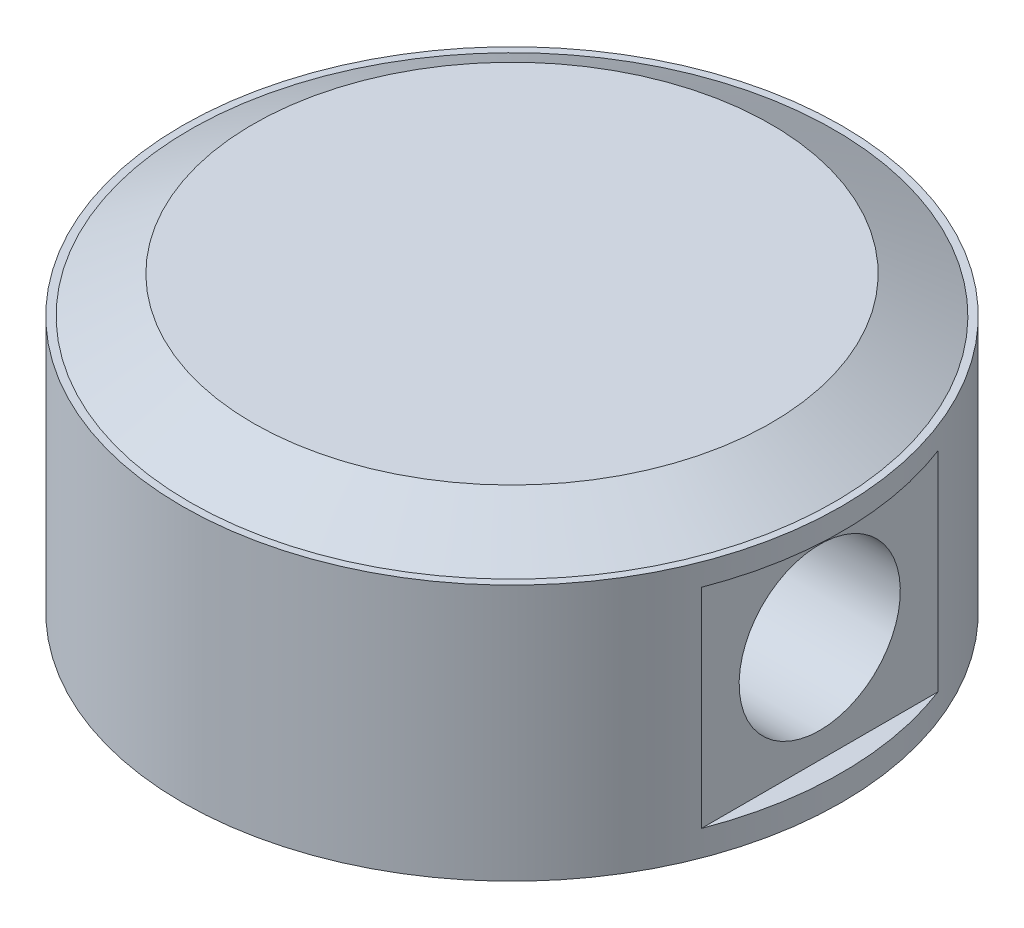
SolidWorks part; units mm, degrees
ref_plane "Front Plane" through (0, 0, 0) normal (0, 0, 1) x (1, 0, 0)
ref_plane "Top Plane" through (0, 0, 0) normal (0, 1, 0) x (1, 0, 0)
ref_plane "Right Plane" through (0, 0, 0) normal (1, 0, 0) x (0, 0, -1)
sketch "Sketch3" plane through (0, 0, 0) normal (0, 0, 1) x (1, 0, 0)
  line L0 (0, 0) -> (0, -5)
  line L1 (0, -5) -> (23.005, -5)
  line L2 (23.005, -5) -> (37, -13.08)
  line L3 (37, -13.08) -> (37, -23.08)
  line L4 (37, -23.08) -> (42, -23.08)
  line L5 (42, -23.08) -> (42, -40)
  line L6 (42, -40) -> (45, -40)
  line L8 (44, -5) -> (35.3397, 0)
  line L9 (35.3397, 0) -> (0, 0)
  line L10 (44, -5) -> (45, -5)
  line L12 (45, -5) -> (45, -40)
  dimension "D1" = 5
  dimension "D2" = 5
  dimension "D3" = 3
  dimension "D4" = 45
  dimension "D5" = 10
  dimension "D6" = 35
  dimension "D7" = 5
  dimension "D8" = 30
  dimension "D9" = 1
  dimension "D10" = 16.92
revolve "Revolve1" add sketch "Sketch3" angle 360 about L0
sketch "Sketch5" plane through (0, -40, 0) normal (0, -1, 0) x (1, 0, 0)
  line L0 (0, -68.5184) -> (0, 57.0205) construction
  line L1 (-73.4461, 0) -> (71.8036, 0) construction
  line L2 (-24.1039, -38) -> (-24.1039, -15)
  line L3 (-24.1039, -15) -> (-14.1039, -15)
  line L4 (-14.1039, -15) -> (-14.1039, 15)
  line L5 (-24.1039, 15) -> (-14.1039, 15)
  line L6 (-24.1039, 38) -> (-24.1039, 15)
  line L7 (24.1039, 38) -> (24.1039, 15)
  line L8 (24.1039, 15) -> (14.1039, 15)
  line L9 (14.1039, -15) -> (14.1039, 15)
  line L10 (24.1039, -15) -> (14.1039, -15)
  line L11 (24.1039, -38) -> (24.1039, -15)
  arc A2 (-24.1039, 38) -> (-24.1039, -38) centre (0, 0) ccw
  arc A3 (24.1039, 38) -> (24.1039, -38) centre (0, 0) cw
  point P10 (-14.1039, 0)
  point P19 (14.1039, 0)
  dimension "D1" = 23
  dimension "D2" = 10
  dimension "D3" = 15
extrude "Boss-Extrude1" add sketch "Sketch5" against normal up to next
sketch "Sketch6" plane through (-14.1039, 0, 0) normal (1, 0, 0) x (0, 0, -1)
  line L0 (35.3397, 0) -> (-35.3397, 0) construction
  circle A0 centre (0, -22) radius 11
  dimension "D1" = 22
  dimension "D2" = 22
extrude "Cut-Extrude1" cut sketch "Sketch6" against normal through all and the other way through all
ref_plane "Plane1" through (0, 0, 45) normal (0, 0, 1) x (1, 0, 0)
sketch "Sketch7" plane through (0, 0, 45) normal (0, 0, 1) x (1, 0, 0)
  line L1 (-45, -5) -> (-45, -11) construction
  line L2 (-45, -33) -> (-45, -36.5)
  line L3 (-45, -8) -> (-45, -11)
  line L6 (45, -36.5) -> (45, -33)
  line L7 (45, -11) -> (45, -8)
  line L8 (-45, -8) -> (-42, -8)
  line L9 (-42, -8) -> (-42, -36.5)
  line L10 (-42, -36.5) -> (-45, -36.5)
  line L11 (0, 0) -> (0, -52.5828) construction
  line L12 (35.3397, 0) -> (-35.3397, 0) construction
  line L13 (42, -36.5) -> (45, -36.5)
  line L14 (45, -8) -> (42, -8)
  line L15 (42, -8) -> (42, -36.5)
  spline S0 degree 2 poles (-45, -11) (-42.3111, -22) (-45, -33) knots 0 0 0 1 1 1 weights 0.034 0.045 0.056 construction
  spline S1 degree 2 poles (-45, -11) (-42.3111, -22) (-45, -33) knots 0 0 0 1 1 1 weights 0.034 0.045 0.056
  spline S2 degree 2 poles (45, -33) (42.3111, -22) (45, -11) knots 0 0 0 1 1 1 weights 0.034 0.045 0.056 construction
  spline S3 degree 2 poles (45, -33) (42.3111, -22) (45, -11) knots 0 0 0 1 1 1 weights 0.034 0.045 0.056
  dimension "D1" = 3
extrude "Cut-Extrude2" cut sketch "Sketch7" against normal through all contours L3 S1 L2 L10 L9 L8 | L6 S3 L7 L14 L15 L13 region at (-43.2093, -22.3261, 45) region at (43.2093, -22.3261, 45)
